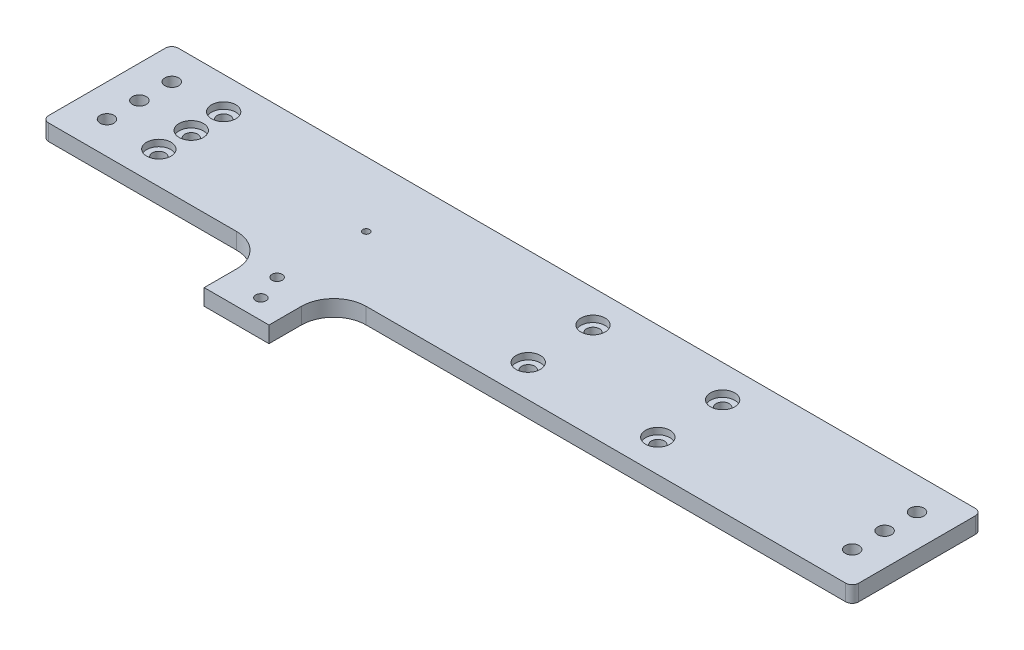
SolidWorks part; units mm, degrees
material "6061-T6 (SS)"
ref_plane "Front" through (0, 0, 0) normal (0, 0, 1) x (1, 0, 0)
ref_plane "Top" through (0, 0, 0) normal (0, 1, 0) x (1, 0, 0)
ref_plane "Right" through (0, 0, 0) normal (1, 0, 0) x (0, 0, -1)
sketch "Sketch1" plane through (0, 0, 0) normal (0, 1, 0) x (1, 0, 0)
  line L1 (-158.75, -25.4) -> (158.75, -25.4)
  line L2 (-158.75, -25.4) -> (-158.75, 25.4)
  line L3 (-158.75, 25.4) -> (158.75, 25.4)
  line L4 (158.75, -25.4) -> (158.75, 25.4)
  line L5 (-158.75, -25.4) -> (158.75, 25.4) construction
  line L6 (-158.75, 25.4) -> (158.75, -25.4) construction
  point P0 (0, 0)
  dimension "D1" = 50.8
  dimension "D2" = 317.5
extrude "Boss-Extrude1" add sketch "Sketch1" along normal blind 6.35
hole_wizard "CBORE for #10 Socket Head Cap Screw1" positions "Sketch2" profile "Sketch4" counterbore size "#10" standard "ANSI Inch" end condition through all
sketch "Sketch2" plane through (0, 6.35, 0) normal (0, 1, 0) x (1, 0, 0)
  line L2 (158.75, 25.4) -> (-158.75, 25.4) construction
  line L6 (-158.75, -25.4) -> (158.75, -25.4) construction
  line L8 (-158.75, 25.4) -> (-158.75, -25.4) construction
  line L12 (158.75, -25.4) -> (158.75, 25.4) construction
  line L15 (19.05, 12.7) -> (19.05, 25.4) construction
  line L17 (19.05, -12.7) -> (19.05, -25.4) construction
  line L18 (-125.73, -25.4) -> (-125.73, -12.7) construction
  line L20 (-125.73, 0) -> (-125.73, 12.7) construction
  line L21 (-125.73, 12.7) -> (-125.73, 25.4) construction
  line L22 (-125.73, 0) -> (-125.73, -12.7) construction
  point P64 (19.05, 12.7)
  point P66 (69.85, 12.7)
  point P68 (19.05, -12.7)
  point P70 (69.85, -12.7)
  point P92 (-125.73, 12.7)
  point P94 (-125.73, 0)
  point P102 (-125.73, -12.7)
  dimension "D2" = 50.8
  dimension "D3" = 25.4
  dimension "D4" = 88.9
  dimension "D5" = 33.02
sketch "Sketch4" plane through (-125.73, 6.35, 12.7) normal (1, 0, 0) x (0, 0, 1)
  line L0 (0, 0) -> (0, 6.35)
  line L1 (0, 6.35) -> (2.5527, 6.35)
  line L3 (2.5527, 6.35) -> (2.5527, 2.54)
  line L4 (2.5527, 2.54) -> (4.7625, 2.54)
  line L5 (4.7625, 2.54) -> (4.7625, 0)
  line L7 (4.7625, 0) -> (0, 0)
  line L11 (0, -6.35) -> (0, 107.95) construction
  dimension "Thru Hole Dia." = 5.1054
  dimension "Thru Hole Depth" = 6.35
  dimension "C'Bore Dia." = 9.525
  dimension "C'Bore Depth" = 2.54
sketch "Sketch7" plane through (0, 0, 0) normal (0, -1, 0) x (1, 0, 0)
  line L0 (-146.05, 25.4) -> (-146.05, 12.7) construction
  line L1 (-158.75, 25.4) -> (158.75, 25.4) construction
  line L2 (-146.05, 12.7) -> (-146.05, 0) construction
  line L3 (-146.05, 0) -> (-146.05, -12.7) construction
  line L4 (-146.05, -12.7) -> (-146.05, -25.4) construction
  line L5 (158.75, -25.4) -> (-158.75, -25.4) construction
  line L7 (-158.75, -25.4) -> (-158.75, 25.4) construction
  line L8 (146.05, 25.4) -> (146.05, 12.7) construction
  line L9 (146.05, 12.7) -> (146.05, 0) construction
  line L10 (146.05, 0) -> (146.05, -12.7) construction
  line L11 (146.05, -12.7) -> (146.05, -25.4) construction
  line L13 (158.75, 25.4) -> (158.75, -25.4) construction
  point P0 (-146.05, 12.7)
  point P2 (-146.05, 0)
  point P4 (-146.05, -12.7)
  point P6 (146.05, 12.7)
  point P8 (146.05, 0)
  point P10 (146.05, -12.7)
  dimension "D1" = 12.7
  dimension "D2" = 12.7
hole_wizard "1/4-28 Tapped Hole1" positions "Sketch7" profile "Sketch6" tap size "1/4-28" standard "ANSI Inch" end condition through all
sketch "Sketch6" plane through (-146.05, 0, 12.7) normal (1, 0, 0) x (0, 0, -1)
  line L0 (0, 0) -> (0, 6.35)
  line L1 (0, 6.35) -> (2.7051, 6.35)
  line L2 (2.7051, 6.35) -> (2.7051, 0)
  line L5 (2.7051, 0) -> (0, 0)
  line L11 (0, -6.35) -> (0, 107.95) construction
  dimension "Thru Tap Drill Dia." = 5.4102
  dimension "Thru Tap Drill Depth" = 6.35
sketch "Sketch10" plane through (0, 0, 0) normal (0, -1, 0) x (-1, 0, 0)
  line L0 (158.75, 25.4) -> (158.75, -25.4) construction
  point P0 (57.15, 0)
  dimension "D1" = 101.6
hole_wizard "#6-32 Tapped Hole1" positions "Sketch10" profile "Sketch9" tap size "#6-32" standard "ANSI Inch" end condition through all
sketch "Sketch9" plane through (-57.15, 0, 0) normal (1, 0, 0) x (0, 0, -1)
  line L0 (0, 0) -> (0, 6.35)
  line L1 (0, 6.35) -> (1.3525, 6.35)
  line L2 (1.3525, 6.35) -> (1.3525, 0)
  line L5 (1.3525, 0) -> (0, 0)
  line L11 (0, -6.35) -> (0, 107.95) construction
  dimension "Thru Tap Drill Dia." = 2.7051
  dimension "Thru Tap Drill Depth" = 6.35
cosmetic thread "Hole Thread1" parameters "D2"=3.5052
sketch "Sketch11" plane through (0, 0, 0) normal (0, -1, 0) x (1, 0, 0)
  line L0 (158.75, -25.4) -> (-158.75, -25.4) construction
  line L1 (-70.0118, -25.4) -> (-48.1024, -25.4)
  line L2 (-70.0118, -25.4) -> (-70.0118, -45.81)
  line L3 (-70.0118, -45.81) -> (-48.1024, -45.81)
  line L4 (-48.1024, -25.4) -> (-48.1024, -45.81)
extrude "Boss-Extrude2" [suppressed] add sketch "Sketch11" against normal up to surface (6.35 mm away) up to face at (-57.15, 6.35, -1.3526)
sketch "Sketch12" plane through (0, 6.35, 0) normal (0, 1, 0) x (1, 0, 0)
  line L0 (-158.75, -25.4) -> (158.75, -25.4) construction
  line L1 (-69.85, -25.4) -> (-44.45, -25.4)
  line L2 (-69.85, -25.4) -> (-69.85, -50.8)
  line L3 (-69.85, -50.8) -> (-44.45, -50.8)
  line L4 (-44.45, -25.4) -> (-44.45, -50.8)
  line L5 (-158.75, 25.4) -> (-158.75, -25.4) construction
  dimension "D1" = 88.9
  dimension "D2" = 25.4
  dimension "D3" = 25.4
extrude "Boss-Extrude3" add sketch "Sketch12" against normal up to surface (6.35 mm away) up to face at (-57.15, 0, -1.3526)
sketch "Sketch15" plane through (0, 0, 0) normal (0, -1, 0) x (-1, 0, 0)
  point P0 (55.245, -43.18)
  point P3 (59.055, -33.02)
hole_wizard "#10-32 Tapped Hole1" positions "Sketch15" profile "Sketch14" tap size "#10-32" standard "ANSI Inch" end condition through all
sketch "Sketch14" plane through (-55.245, 0, 43.18) normal (1, 0, 0) x (0, 0, -1)
  line L0 (0, 0) -> (0, 6.35)
  line L1 (0, 6.35) -> (2.0193, 6.35)
  line L2 (2.0193, 6.35) -> (2.0193, 0)
  line L5 (2.0193, 0) -> (0, 0)
  line L11 (0, -6.35) -> (0, 107.95) construction
  dimension "Thru Tap Drill Dia." = 4.0386
  dimension "Thru Tap Drill Depth" = 6.35
fillet "Fillet1" radius 12.7 2 edges at (-69.85, 3.175, 25.4) (-44.45, 3.175, 25.4)
fillet "Fillet2" radius 2.54 4 edges at (158.75, 3.175, 25.4) (158.75, 3.175, -25.4) (-158.75, 3.175, -25.4) (-158.75, 3.175, 25.4)
